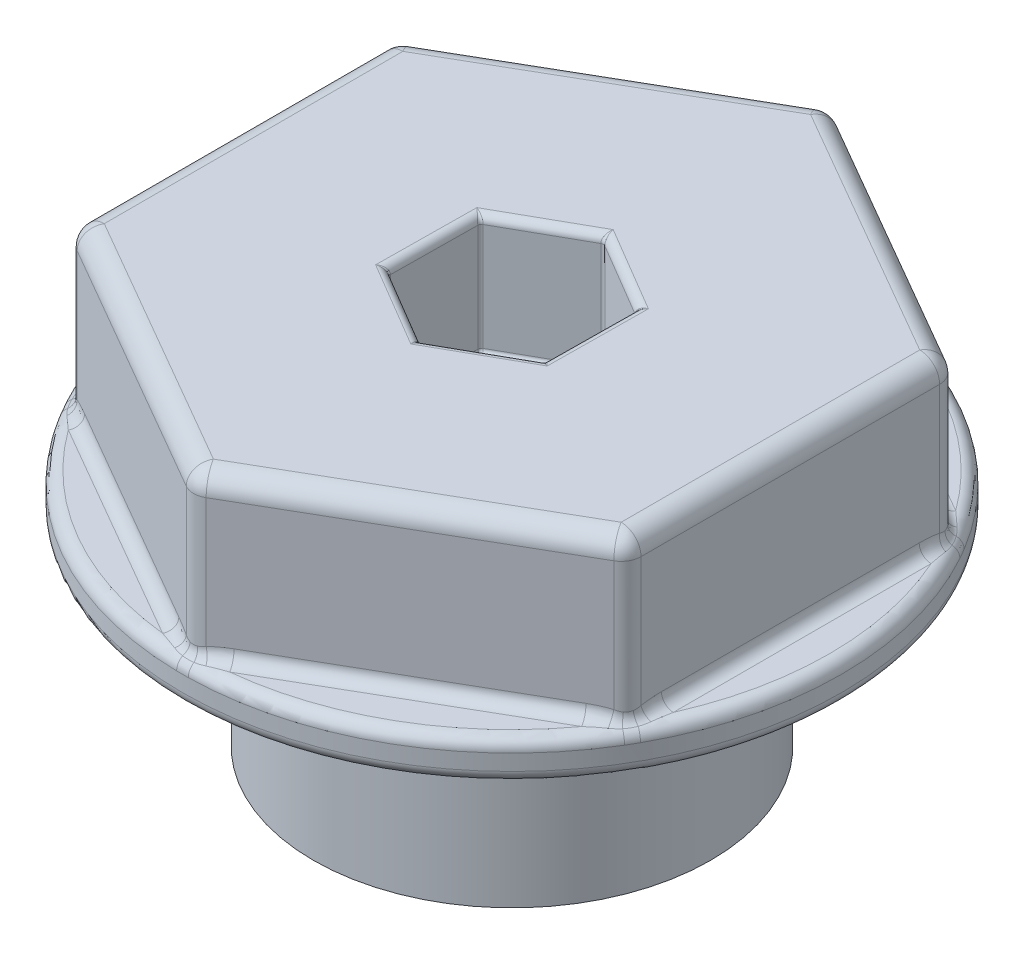
SolidWorks part; units mm, degrees
material "moto_grey"
ref_plane "Front Plane" through (0, 0, 0) normal (0, 0, 1) x (1, 0, 0)
ref_plane "Top Plane" through (0, 0, 0) normal (0, 1, 0) x (1, 0, 0)
ref_plane "Right Plane" through (0, 0, 0) normal (1, 0, 0) x (0, 0, -1)
sketch "Sketch1" plane through (0, 0, 0) normal (0, 1, 0) x (1, 0, 0)
  circle A0 centre (0, 0) radius 5
  dimension "D1" = 10
extrude "Boss-Extrude1" add sketch "Sketch1" along normal blind 5
sketch "Sketch2" plane through (0, 5, 0) normal (0, 1, 0) x (1, 0, 0)
  line L2 (7.0043, -4.0463) -> (7.0064, 4.0428)
  line L3 (7.0064, 4.0428) -> (0.002, 8.0891)
  line L4 (0.002, 8.0891) -> (-7.0043, 4.0463)
  line L5 (-7.0043, 4.0463) -> (-7.0064, -4.0428)
  line L6 (-7.0064, -4.0428) -> (-0.002, -8.0891)
  line L7 (-0.002, -8.0891) -> (7.0043, -4.0463)
  circle A1 centre (0, 0) radius 7.0053 construction
extrude "Boss-Extrude2" add sketch "Sketch2" along normal blind 5
fillet "Fillet1" radius 0.5 18 edges at (7.0053, 10, 0.0018) (7.0053, 5, 0.0018) (3.5011, 10, 6.0677) (7.0043, 7.5, 4.0463) (3.5011, 5, 6.0677) (-3.5042, 10, 6.0659) (-0.002, 7.5, 8.0891) (-3.5042, 5, 6.0659) (-7.0053, 10, -0.0018) (-7.0064, 7.5, 4.0428) (-7.0053, 5, -0.0018) (-3.5011, 10, -6.0677) (-7.0043, 7.5, -4.0463) (-3.5011, 5, -6.0677) (7.0064, 7.5, -4.0428) (3.5042, 10, -6.0659) (0.002, 7.5, -8.0891) (3.5042, 5, -6.0659)
sketch "Sketch3" plane through (0, 5, 0) normal (0, -1, 0) x (1, 0, 0)
  circle A0 centre (0, 0) radius 8.2926
extrude "Boss-Extrude3" add sketch "Sketch3" against normal blind 1
fillet "Fillet2" radius 0.3 1 edges at (0, 6, -8.2926)
fillet "Fillet3" radius 0.3 1 edges at (0, 5, -8.2926)
fillet "Fillet5" radius 0.3 24 edges at (0.1991, 6, -7.9712) (0.002, 6, -8.0117) (-0.1951, 6, -7.9713) (-3.5011, 6, -6.0677) (-6.8037, 6, -4.158) (-6.9374, 6, -4.0076) (-7.0009, 6, -3.8167) (-7.0053, 6, -0.0018) (-7.0028, 6, 3.8132) (-6.9394, 6, 4.0041) (-6.8058, 6, 4.1546) (-3.5042, 6, 6.0659) (-0.1991, 6, 7.9712) (-0.002, 6, 8.0117) (0.1951, 6, 7.9713) (3.5011, 6, 6.0677) (6.8037, 6, 4.158) (6.9374, 6, 4.0076) (7.0009, 6, 3.8167) (7.0053, 6, 0.0018) (7.0028, 6, -3.8132) (6.9394, 6, -4.0041) (6.8058, 6, -4.1546) (3.5042, 6, -6.0659)
sketch "Sketch4" plane through (0, 10, 0) normal (0, 1, 0) x (1, 0, 0)
  line L1 (1.9947, 1.1229) -> (0.0249, 2.2889)
  line L2 (0.0249, 2.2889) -> (-1.9698, 1.166)
  line L3 (-1.9698, 1.166) -> (-1.9947, -1.1229)
  line L4 (-1.9947, -1.1229) -> (-0.0249, -2.2889)
  line L5 (-0.0249, -2.2889) -> (1.9698, -1.166)
  line L6 (1.9698, -1.166) -> (1.9947, 1.1229)
  circle A0 centre (0, 0) radius 1.9823 construction
extrude "Cut-Extrude1" cut sketch "Sketch4" against normal blind 3
fillet "Fillet6" radius 0.2 6 edges at (1.0098, 10, -1.7059) (-0.9724, 10, -1.7274) (-1.9822, 10, -0.0216) (-1.0098, 10, 1.7059) (0.9724, 10, 1.7274) (1.9822, 10, 0.0216)
fillet "Fillet7" radius 0.1 18 edges at (2.0536, 9.9414, -1.156) (2.028, 9.9414, 1.2004) (-0.0256, 9.9414, 2.3565) (-2.0536, 9.9414, 1.156) (-2.028, 9.9414, -1.2004) (0.0256, 9.9414, -2.3565) (0.9724, 7, 1.7274) (-1.0098, 7, 1.7059) (-1.9822, 7, -0.0216) (-0.9724, 7, -1.7274) (1.0098, 7, -1.7059) (1.9822, 7, 0.0216) (1.9947, 8.4, -1.1229) (1.9698, 8.4, 1.166) (-0.0249, 8.4, 2.2889) (-1.9947, 8.4, 1.1229) (-1.9698, 8.4, -1.166) (0.0249, 8.4, -2.2889)
